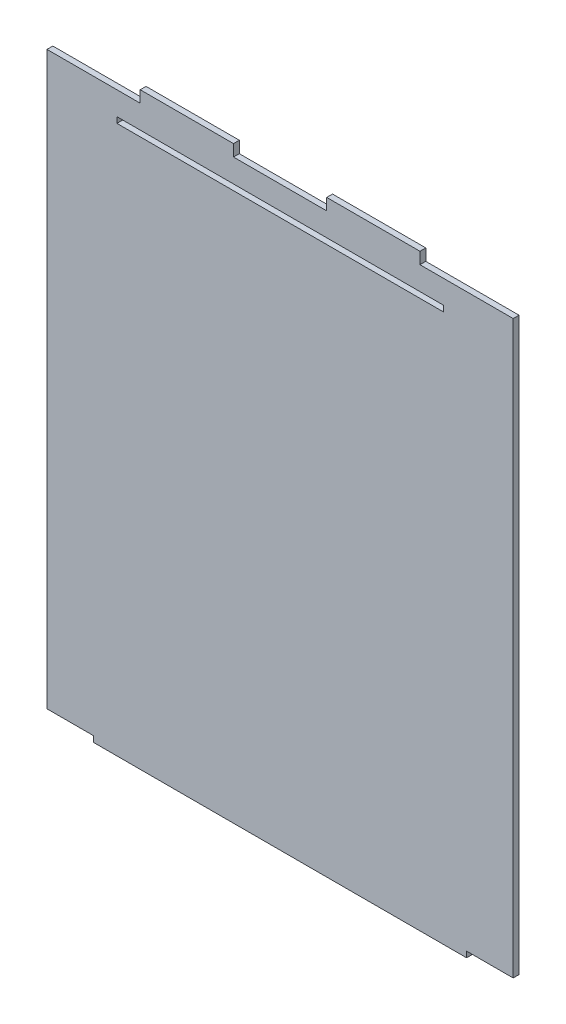
SolidWorks part; units mm, degrees
ref_plane "Front Plane" through (0, 0, 0) normal (0, 0, 1) x (1, 0, 0)
ref_plane "Top Plane" through (0, 0, 0) normal (0, 1, 0) x (1, 0, 0)
ref_plane "Right Plane" through (0, 0, 0) normal (1, 0, 0) x (0, 0, -1)
sketch "Sketch1" plane through (0, 0, 0) normal (0, 0, 1) x (1, 0, 0)
  line L0 (0, -9.525) -> (25.4, -9.525)
  line L1 (25.4, -12.7) -> (228.6, -12.7)
  line L2 (0, -9.525) -> (0, 301.625)
  line L3 (50.8, 307.975) -> (101.6, 307.975)
  line L4 (254, -9.525) -> (254, 301.625)
  line L5 (25.4, -9.525) -> (25.4, -12.7)
  line L6 (25.4, -12.7) -> (228.6, -12.7)
  line L7 (0, 301.625) -> (50.8, 301.625)
  line L8 (50.8, 301.625) -> (50.8, 307.975)
  line L9 (50.8, 307.975) -> (101.6, 307.975)
  line L10 (101.6, 307.975) -> (101.6, 301.625)
  line L11 (101.6, 301.625) -> (152.4, 301.625)
  line L12 (152.4, 301.625) -> (152.4, 307.975)
  line L13 (152.4, 307.975) -> (203.2, 307.975)
  line L14 (203.2, 307.975) -> (203.2, 301.625)
  line L15 (203.2, 301.625) -> (254, 301.625)
  line L16 (152.4, 307.975) -> (203.2, 307.975)
  line L17 (228.6, -12.7) -> (228.6, -9.525)
  line L18 (228.6, -9.525) -> (254, -9.525)
  line L20 (38.1, 288.925) -> (215.9, 288.925)
  line L21 (38.1, 288.925) -> (38.1, 285.75)
  line L22 (38.1, 285.75) -> (215.9, 285.75)
  line L23 (215.9, 288.925) -> (215.9, 285.75)
  dimension "D1" = 320.675
  dimension "D2" = 3.175
  dimension "D3" = 6.35
  dimension "D4" = 50.8
  dimension "D5" = 50.8
  dimension "D6" = 50.8
  dimension "D7" = 50.8
  dimension "D8" = 50.8
  dimension "D9" = 3.175
  dimension "D10" = 25.4
  dimension "D11" = 25.4
  dimension "D12" = 3.175
  dimension "D13" = 177.8
  dimension "D14" = 38.1
  dimension "D15" = 12.7
extrude "Boss-Extrude1" add sketch "Sketch1" along normal blind 3.175 contours L17 L18 L4 L15 L14 L13 L12 L11 L10 L3 L8 L7 L2 L0 L5 L1 L20 L23 L22 L21 region at (127, 145.0628, 0)
